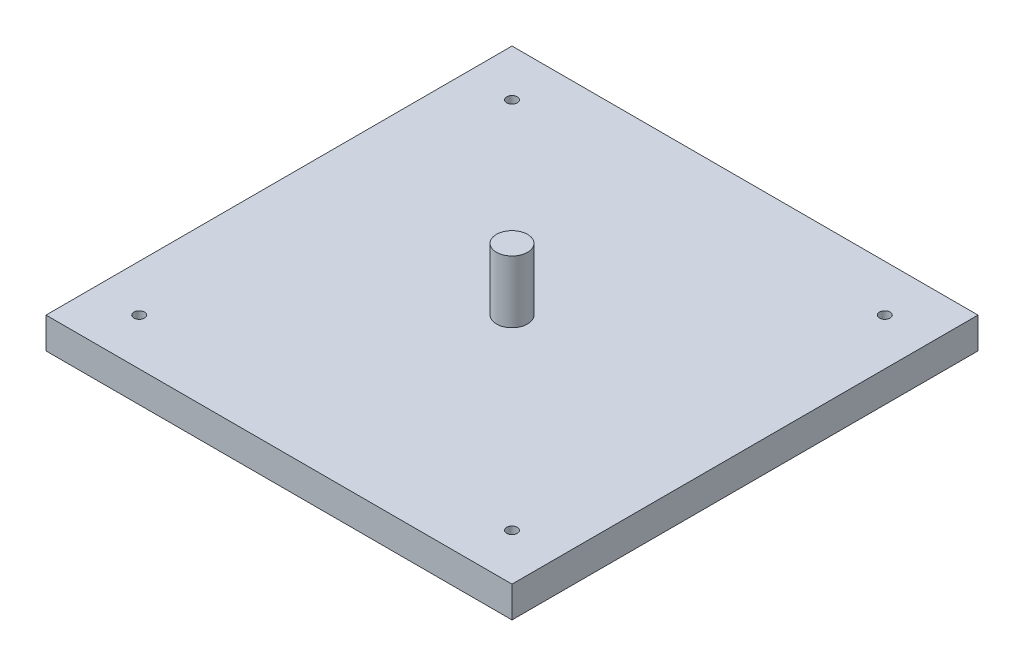
SolidWorks part; units mm, degrees
ref_plane "Front Plane" through (0, 0, 0) normal (0, 0, 1) x (1, 0, 0)
ref_plane "Top Plane" through (0, 0, 0) normal (0, 1, 0) x (1, 0, 0)
ref_plane "Right Plane" through (0, 0, 0) normal (1, 0, 0) x (0, 0, -1)
sketch "Sketch2" plane through (0, 0, 0) normal (0, 1, 0) x (1, 0, 0)
  line L0 (0, 75) -> (0, -75) construction
  line L1 (-75, -75) -> (75, -75)
  line L2 (-75, -75) -> (-75, 75)
  line L3 (-75, 75) -> (75, 75)
  line L4 (75, -75) -> (75, 75)
  line L5 (-75, -75) -> (75, 75) construction
  line L6 (-75, 75) -> (75, -75) construction
  line L7 (-75, 0) -> (75, 0) construction
  circle A0 centre (-60, 60) radius 1.7
  circle A1 centre (60, 60) radius 1.7
  circle A2 centre (60, -60) radius 1.7
  circle A3 centre (-60, -60) radius 1.7
  circle A4 centre (0, 0) radius 5
  point P0 (0, 0)
  dimension "D3" = 3.4
  dimension "D5" = 10
  dimension "D1" = 150
  dimension "D2" = 150
  dimension "D4" = 60
extrude "Boss-Extrude1" add sketch "Sketch2" along normal blind 10 contours L1 L4 L3 L2 A1 A0 A2 A3 region at (-72.8787, 0, 0)
extrude "Boss-Extrude2" add sketch "Sketch2<3>" along normal blind 30 contours A4 region at (0, 0, 0)
sketch "Sketch2<3>" plane through (0, 0, 0) normal (0, 1, 0) x (1, 0, 0) same geometry as "Sketch2"
